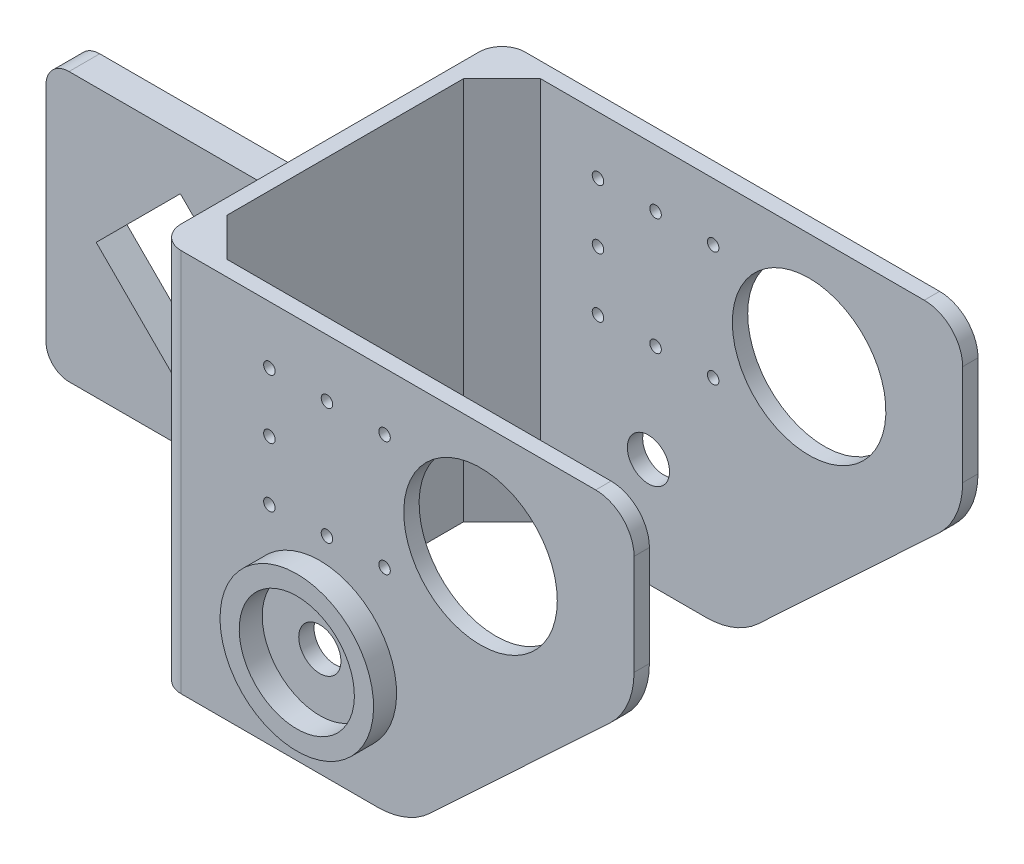
SolidWorks part; units mm, degrees
ref_plane "前视基准面" through (0, 0, 0) normal (0, 0, 1) x (1, 0, 0)
ref_plane "上视基准面" through (0, 0, 0) normal (0, 1, 0) x (1, 0, 0)
ref_plane "右视基准面" through (0, 0, 0) normal (1, 0, 0) x (0, 0, -1)
sketch "草图3" plane through (0, 0, 0) normal (0, 0, 1) x (1, 0, 0)
  line L0 (60.2665, 6.5325) -> (60.2665, 16.5325)
  line L1 (10.7665, 16.5325) -> (10.7665, 6.5325)
  line L2 (10.7665, 16.5325) -> (60.2665, 16.5325)
  circle A0 centre (60.2665, 16.5325) radius 3
  circle A1 centre (60.2665, 6.5325) radius 3
  circle A6 centre (10.7665, 6.5325) radius 3
  circle A7 centre (10.7665, 16.5325) radius 3
  dimension "D1" = 6
  dimension "D2" = 6
  dimension "D4" = 6
  dimension "D5" = 6
  dimension "D3" = 10
  dimension "D6" = 49.5
  dimension "D7" = 49.5
  dimension "D8" = 10
extrude "凸台-拉伸6" add sketch "草图3" along normal blind 0.001 contours A6 | A0 | A1 | A7
sketch "草图11" plane through (0, 0, 0.001) normal (0, 0, 1) x (1, 0, 0)
  circle A0 centre (10.7665, 16.5325) radius 2.25
  circle A1 centre (10.7665, 6.5325) radius 2.25
  circle A2 centre (60.2665, 16.5325) radius 2.25
  circle A3 centre (60.2665, 6.5325) radius 2.25
  dimension "D1" = 4.5
  dimension "D2" = 4.5
  dimension "D3" = 4.5
  dimension "D4" = 4.5
extrude "切除-拉伸2" cut sketch "草图11" against normal through all both and the other way through all
sketch "草图12" plane through (0, 0, 0.001) normal (0, 0, 1) x (1, 0, 0)
  line L4 (10.7665, 16.5325) -> (60.2665, 6.5325) construction
  line L5 (10.7665, 6.5325) -> (60.2665, 16.5325) construction
  line L6 (60.2665, 16.5325) -> (60.2665, 6.5325) construction
  line L7 (5.5165, 26.5325) -> (65.5165, 26.5325)
  line L8 (5.5165, 26.5325) -> (5.5165, 1.5325)
  line L9 (5.5165, -23.4675) -> (65.5165, -23.4675)
  line L10 (65.5165, 26.5325) -> (65.5165, -23.4675)
  line L11 (5.5165, 1.5325) -> (5.5165, -23.4675) construction
  line L13 (5.5165, -23.4675) -> (5.5165, 1.5325) construction
  line L16 (5.5165, 1.5325) -> (5.5165, -23.4675)
  circle A4 centre (45.5165, 11.5325) radius 10
  point P8 (35.5165, 11.5325)
  point P9 (35.5165, 26.5325)
  point P10 (-46.6091, 14.6442)
  point P11 (60.2665, 11.5325)
  dimension "D5" = 20
  dimension "D1" = 60
  dimension "D2" = 50
  dimension "D3" = 15
  dimension "D4" = 14.75
extrude "凸台-拉伸7" add sketch "草图12" along normal blind 2 and the other way blind 0.8019 contours L7 L10 L9 L16 L8
sketch "草图14" plane through (0, 0, -0.8009) normal (0, 0, -1) x (-1, 0, 0)
  line L0 (-60.2665, 16.5325) -> (-60.2665, 6.5325) construction
  circle A8 centre (-45.5165, 11.5325) radius 10
  point P14 (-60.2665, 11.5325)
  point P15 (0.1696, -0.033)
  dimension "D2" = 20
extrude "切除-拉伸3" cut sketch "草图14" against normal blind 3
sketch "草图15" plane through (0, 0, -0.8009) normal (0, 0, -1) x (-1, 0, 0)
  circle A0 centre (-45.5165, 11.5325) radius 10 construction
  circle A1 centre (-45.5165, 11.5325) radius 10
  circle A2 centre (-45.5165, -12.4675) radius 2.75
  dimension "D2" = 5.5
  dimension "D1" = 24
extrude "凸台-拉伸10" add sketch "草图12<4>" along normal blind 44
sketch "草图12<4>" plane through (0, 0, 0.001) normal (0, 0, 1) x (1, 0, 0) same geometry as "草图12"
sketch "草图19" plane through (65.5165, 0, 0) normal (1, 0, 0) x (0, 0, -1)
  line L0 (-44.001, 26.5325) -> (-42.001, 26.5325)
  line L1 (-44.001, 26.5325) -> (0.8009, 26.5325) construction
  line L2 (0.8009, 26.5325) -> (-1.1991, 26.5325)
  dimension "D1" = 2
  dimension "D2" = 2
sketch "草图20" plane through (65.5165, 0, 0) normal (1, 0, 0) x (0, 0, -1)
  line L0 (-42.001, 26.5325) -> (-42.001, -23.4675)
  line L1 (-44.001, -23.4675) -> (0.8009, -23.4675) construction
  line L2 (-42.001, 26.5325) -> (-1.1991, 26.5325)
  line L3 (-1.1991, 26.5325) -> (-1.1991, -23.4675)
  line L4 (-1.1991, -23.4675) -> (-42.001, -23.4675)
extrude "切除-拉伸6" cut sketch "草图20" against normal blind 60
sketch "草图21" plane through (5.5165, 0, 0) normal (-1, 0, 0) x (0, 0, 1)
  line L0 (-0.8009, -23.4675) -> (44.001, -23.4675)
  line L1 (44.001, -23.4675) -> (44.001, 26.5325)
  line L2 (44.001, 26.5325) -> (-0.8009, 26.5325)
  line L3 (-0.8009, 26.5325) -> (-0.8009, -23.4675)
extrude "凸台-拉伸11" add sketch "草图21" along normal blind 2
sketch "草图23" plane through (3.5165, 0, 0) normal (-1, 0, 0) x (0, 0, 1)
  line L3 (19.6, 19.0325) -> (23.6, 19.0325)
  line L4 (19.6, 19.0325) -> (19.6, -15.9675)
  line L5 (19.6, -15.9675) -> (23.6, -15.9675)
  line L6 (23.6, 19.0325) -> (23.6, -15.9675)
  line L7 (19.6, 19.0325) -> (23.6, -15.9675) construction
  line L8 (19.6, -15.9675) -> (23.6, 19.0325) construction
  point P9 (21.6, 1.5325)
  dimension "D1" = 35
  dimension "D2" = 4
extrude "凸台-拉伸12" add sketch "草图23" along normal blind 35
sketch "草图24" plane through (0, 0, 23.6) normal (0, 0, 1) x (1, 0, 0)
  line L17 (-13.9835, 12.4925) -> (-24.9437, 1.5323)
  line L18 (-24.9437, 1.5323) -> (-13.9835, -9.4278)
  line L19 (-13.9835, -9.4278) -> (-3.0234, 1.5323)
  line L20 (-3.0234, 1.5323) -> (-13.9835, 12.4925)
extrude "切除-拉伸7" cut sketch "草图24" against normal through all
sketch "草图25" plane through (0, 0, -0.8009) normal (0, 0, -1) x (-1, 0, 0)
  circle A0 centre (-33.0165, 19.0325) radius 0.75
  circle A2 centre (-33.0165, 4.0325) radius 0.75
  circle A3 centre (-18.0165, 19.0325) radius 0.75
  circle A4 centre (-18.0165, 3.623) radius 0.75
  circle A5 centre (-25.5165, 19.0325) radius 0.75
  circle A6 centre (-25.5165, 3.8277) radius 0.75
  circle A7 centre (-18.0165, 11.3277) radius 0.75
  dimension "D4" = 15
  dimension "D5" = 1.5
  dimension "D1" = 1.5
  dimension "D2" = 1.5
  dimension "D3" = 1.5
  dimension "D6" = 1.5
  dimension "D7" = 1.5
  dimension "D8" = 1.5
extrude "切除-拉伸8" cut sketch "草图25" against normal through all
fillet "圆角2" radius 5 1 edges at (65.5165, 26.5325, 0.1991)
fillet "圆角3" radius 5 1 edges at (65.5165, 26.5325, 43.001)
fillet "圆角5" radius 3 1 edges at (3.5165, 1.5325, 44.001)
fillet "圆角6" radius 3 1 edges at (3.5165, 1.5325, -0.8009)
fillet "圆角7" radius 3 1 edges at (-31.4835, -15.9675, 21.6)
fillet "圆角8" radius 3 1 edges at (-31.4835, 19.0325, 21.6)
sketch "草图26" plane through (0, 0, -0.8009) normal (0, 0, -1) x (-1, 0, 0)
  circle A0 centre (-24.5861, -9.3979) radius 2.75
  dimension "D1" = 5.5
  dimension "D2" = 29.6
extrude "切除-拉伸9" cut sketch "草图26" against normal blind 100
sketch "草图27" plane through (0, 0, 1.1991) normal (0, 0, 1) x (1, 0, 0)
  circle A0 centre (24.5861, -9.3979) radius 7.5
  circle A1 centre (24.5861, -9.3979) radius 10
  dimension "D1" = 15
  dimension "D2" = 20
extrude "凸台-拉伸13" add sketch "草图27" against normal blind 5
sketch "草图28" plane through (0, 0, 42.001) normal (0, 0, -1) x (-1, 0, 0)
  circle A0 centre (-24.5861, -9.3979) radius 7.5
  circle A1 centre (-24.5861, -9.3979) radius 10
  dimension "D1" = 15
  dimension "D2" = 20
extrude "凸台-拉伸14" add sketch "草图28" against normal blind 5
sketch "草图29" plane through (0, 0, -0.8009) normal (0, 0, -1) x (-1, 0, 0)
  line L0 (-65.5165, 21.5325) -> (-65.5165, -23.4675) construction
  line L1 (-65.5165, 4.1055) -> (-36.0165, -23.4675)
  line L2 (-6.5165, -23.4675) -> (-65.5165, -23.4675) construction
  line L3 (-36.0165, -23.4675) -> (-65.5165, -23.4675)
  line L4 (-65.5165, -23.4675) -> (-65.5165, 4.1055)
extrude "切除-拉伸10" cut sketch "草图29" against normal through all
sketch "草图31" plane through (0, 0, -0.8009) normal (0, 0, -1) x (-1, 0, 0)
  line L0 (-36.0165, -23.4675) -> (-38.8991, -20.7731)
  line L2 (-36.0165, -23.4675) -> (-32.0707, -23.4675)
  arc A0 (-32.0707, -23.4675) -> (-38.8991, -20.7731) centre (-32.0707, -13.4675) cw
  point P10 (-36.0165, -23.4675)
  dimension "D1" = 10
  dimension "D2" = 2.8826
extrude "切除-拉伸11" cut sketch "草图31" against normal through all
sketch "草图32" plane through (0, 0, -0.8009) normal (0, 0, -1) x (-1, 0, 0)
  line L0 (-65.5165, 8.4468) -> (-65.5165, 4.1055)
  line L2 (-65.5165, 4.1055) -> (-62.3449, 1.1411)
  arc A0 (-62.3449, 1.1411) -> (-65.5165, 8.4468) centre (-55.5165, 8.4468) cw
  point P10 (-65.5165, 4.1055)
  dimension "D1" = 10
extrude "切除-拉伸12" cut sketch "草图32" against normal through all
sketch "草图35" plane through (0, -23.4675, 0) normal (0, -1, 0) x (1, 0, 0)
  line L0 (5.5165, 42.001) -> (10.5165, 42.001)
  line L1 (5.5165, 42.001) -> (32.0707, 42.001) construction
  line L2 (10.5165, 42.001) -> (5.5165, 37.001)
  line L3 (5.5165, 1.1991) -> (5.5165, 42.001) construction
  line L4 (5.5165, 37.001) -> (5.5165, 42.001)
  line L5 (5.5165, 1.1991) -> (5.5165, 6.1991)
  line L6 (5.5165, 6.1991) -> (10.5165, 1.1991)
  line L7 (5.5165, 1.1991) -> (32.0707, 1.1991) construction
  line L8 (10.5165, 1.1991) -> (5.5165, 1.1991)
  dimension "D1" = 5
  dimension "D2" = 5
  dimension "D3" = 5
  dimension "D4" = 5
extrude "凸台-拉伸15" add sketch "草图35" against normal blind 50
